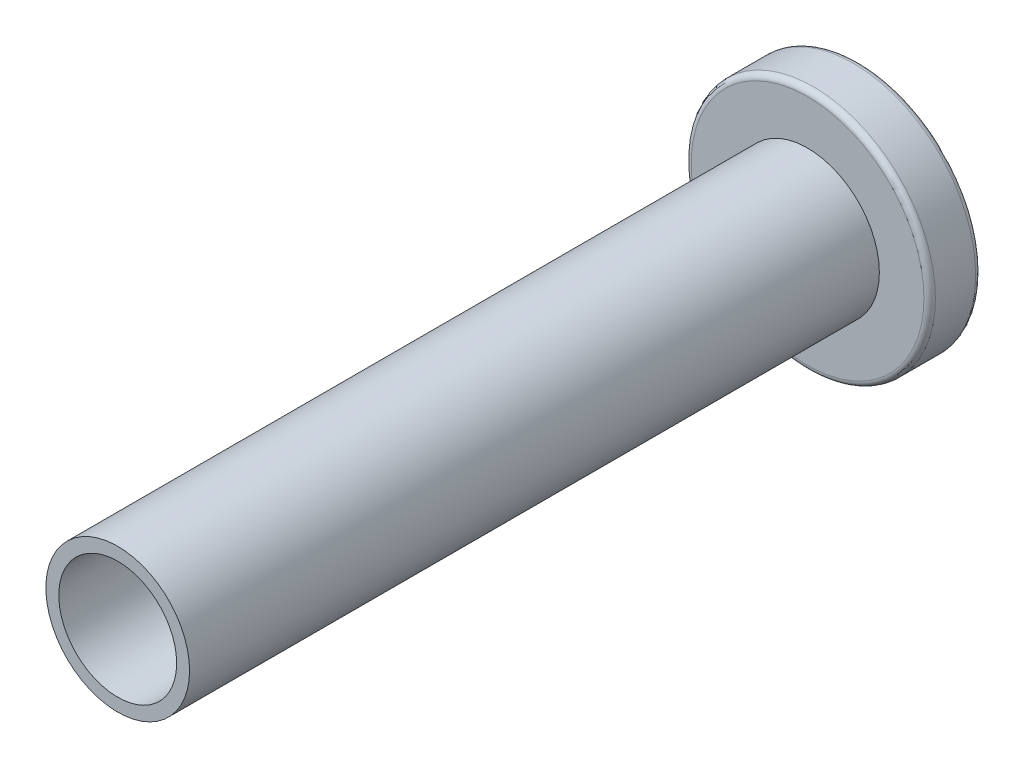
SolidWorks part; units mm, degrees
material "AISI 304"
ref_plane "前视基准面" through (0, 0, 0) normal (0, 0, 1) x (1, 0, 0)
ref_plane "上视基准面" through (0, 0, 0) normal (0, 1, 0) x (1, 0, 0)
ref_plane "右视基准面" through (0, 0, 0) normal (1, 0, 0) x (0, 0, -1)
other "Configuration Table"
sketch "草图1" plane through (0, 0, 0) normal (0, 0, 1) x (1, 0, 0)
  circle A0 centre (0, 0) radius 4.25
  dimension "D1" = 8.5
extrude "凸台-拉伸1" add sketch "草图1" along normal blind 1.8
sketch "草图2" plane through (0, 0, 1.8) normal (0, 0, 1) x (1, 0, 0)
  circle A0 centre (0, 0) radius 2.5
  circle A1 centre (0, 0) radius 2.05
  dimension "D1" = 5
  dimension "D2" = 4.1
extrude "凸台-拉伸2" add sketch "草图2" along normal blind 24
fillet "圆角1" radius 0.2 2 edges at (4.25, 0, 0) (4.25, 0, 1.8)
sketch "草图3" plane through (0, 0, 0) normal (0, 0, -1) x (-1, 0, 0)
  line L0 (0, 0) -> (1.4434, 0) construction
  line L1 (1.4434, 0) -> (0.7217, 1.25)
  line L2 (0.7217, 1.25) -> (-0.7217, 1.25)
  line L3 (-0.7217, 1.25) -> (-1.4434, 0)
  line L4 (-1.4434, 0) -> (-0.7217, -1.25)
  line L5 (-0.7217, -1.25) -> (0.7217, -1.25)
  line L6 (0.7217, -1.25) -> (1.4434, 0)
  circle A0 centre (0, 0) radius 1.25 construction
  dimension "D1" = 2.5
extrude "切除-拉伸1" cut sketch "草图3" against normal blind 1.5
